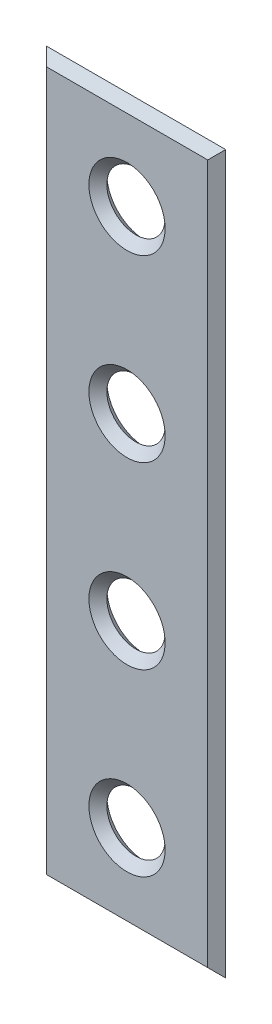
SolidWorks part; units mm, degrees
ref_plane "前视" through (0, 0, 0) normal (0, 0, 1) x (1, 0, 0)
ref_plane "上视" through (0, 0, 0) normal (0, 1, 0) x (1, 0, 0)
ref_plane "右视" through (0, 0, 0) normal (1, 0, 0) x (0, 0, -1)
sketch "草图1" plane through (0, 0, 0) normal (0, 0, 1) x (1, 0, 0)
  line L0 (40, 352.4218) -> (40, -138.3119) construction
  line L1 (0, 0) -> (80, 0)
  line L2 (0, 0) -> (0, 320)
  line L3 (0, 320) -> (80, 320)
  line L4 (80, 0) -> (80, 320)
  circle A0 centre (40, 280) radius 13
  circle A1 centre (40, 200) radius 13
  circle A2 centre (40, 120) radius 13
  circle A3 centre (40, 40) radius 13
  dimension "D3" = 26
  dimension "D1" = 320
  dimension "D2" = 80
  dimension "D4" = 40
  dimension "D5" = 80
  dimension "D6" = 80
  dimension "D7" = 80
extrude "基体-拉伸" add sketch "草图1" along normal blind 8
chamfer "倒角1" distance 4 angle 45 16 edges at (53, 40, 0) (53, 200, 0) (40, 0, 0) (80, 160, 0) (40, 320, 0) (0, 160, 0) (53, 280, 0) (53, 120, 0) (53, 40, 8) (53, 200, 8) (40, 320, 8) (80, 160, 8) (40, 0, 8) (0, 160, 8) (53, 280, 8) (53, 120, 8)
